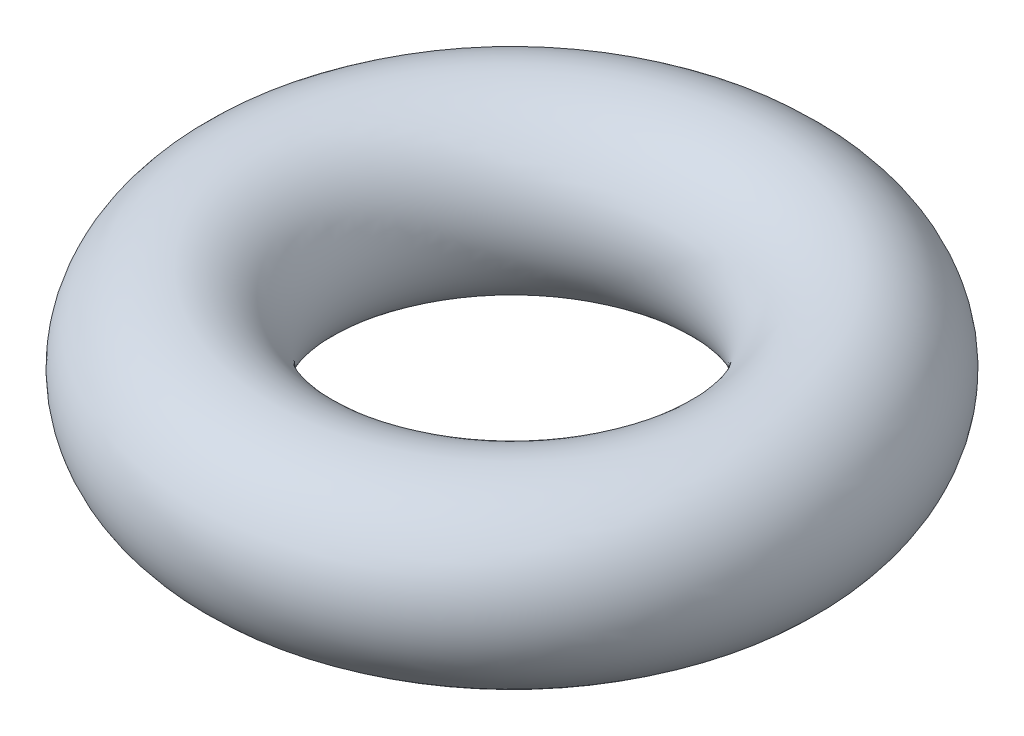
SolidWorks part; units mm, degrees
material "Polyester Resin"
ref_plane "Front Plane" through (0, 0, 0) normal (0, 0, 1) x (1, 0, 0)
ref_plane "Top Plane" through (0, 0, 0) normal (0, 1, 0) x (1, 0, 0)
ref_plane "Right Plane" through (0, 0, 0) normal (1, 0, 0) x (0, 0, -1)
sketch "Sketch1" plane through (0, 0, 0) normal (1, 0, 0) x (0, 0, -1)
  line L0 (0, 0.6106) -> (0, 0) construction
  line L1 (0, 0) -> (2.75, 0) construction
  circle A0 centre (2.75, 0) radius 1
  dimension "D2" = 2
  dimension "D1" = 2.75
revolve "Revolve1" add sketch "Sketch1" angle 360 about L0
ref_axis "Axis1" through (0, -0.825, 0) along (0, 1, 0)
